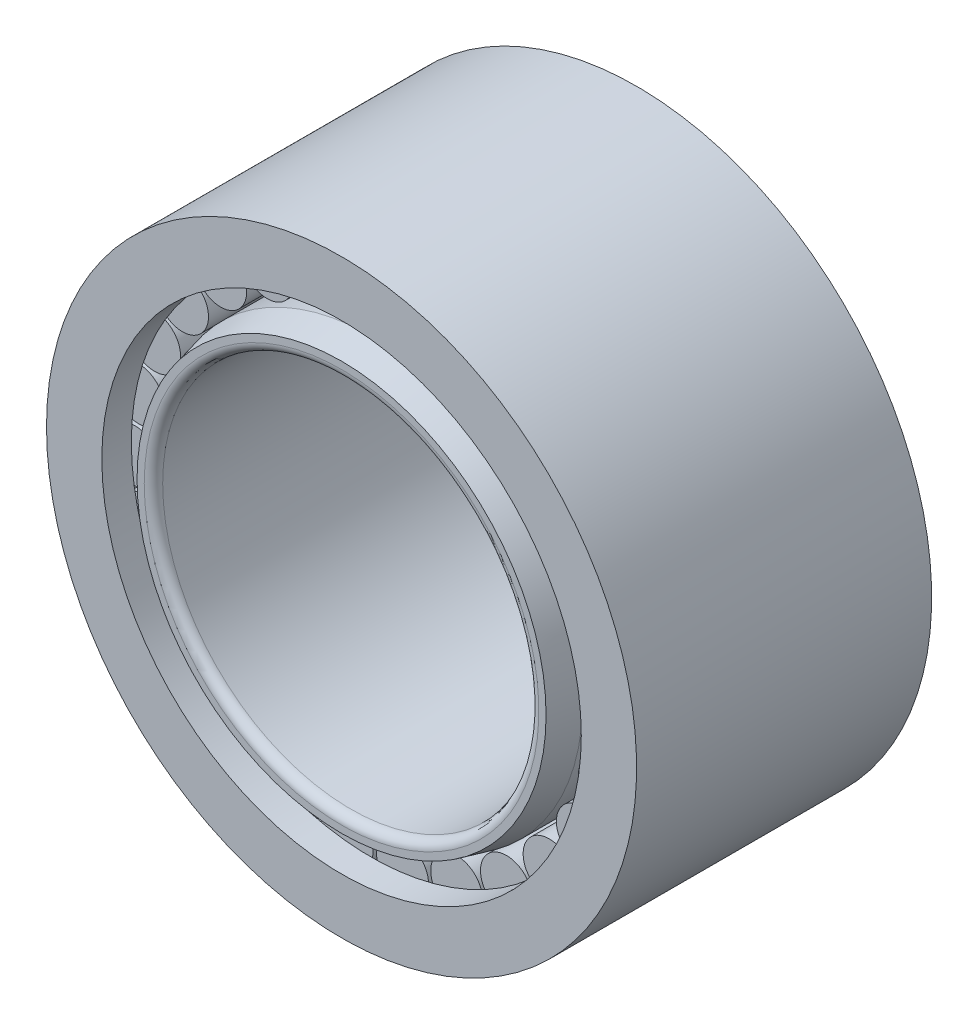
SolidWorks part; units mm, degrees
ref_plane "Front Plane" through (0, 0, 0) normal (0, 0, 1) x (1, 0, 0)
ref_plane "Top Plane" through (0, 0, 0) normal (0, 1, 0) x (1, 0, 0)
ref_plane "Right Plane" through (0, 0, 0) normal (1, 0, 0) x (0, 0, -1)
sketch "Sketch1" plane through (0, 0, 0) normal (1, 0, 0) x (0, 0, -1)
  line L0 (-8, 13) -> (-8, 16)
  line L1 (-8, 16) -> (8, 16)
  line L2 (8, 16) -> (8, 13)
  line L3 (8, 13) -> (6.4, 13)
  line L4 (6.4, 13) -> (6.4, 14.53)
  line L5 (6.4, 14.53) -> (-6.4, 14.53)
  line L6 (-6.4, 14.53) -> (-6.4, 13)
  line L7 (-6.4, 13) -> (-8, 13)
  point P7 (0, 14.53)
  dimension "D1" = 16
  dimension "D2" = 14.53
  dimension "D3" = 13
  dimension "D4" = 1.6
  dimension "D5" = 16
ref_axis "Axis1" through (0, 0, -22) along (0, 0, 1)
revolve "Revolve1" add sketch "Sketch1" angle 360 about axis through (0, 0, -22) along (0, 0, 1)
sketch "Sketch2" plane through (0, 0, 0) normal (1, 0, 0) x (0, 0, -1)
  line L0 (7.5, 10.2) -> (-7.5, 10.2)
  line L1 (-8, 11.09) -> (-6.4, 11.47)
  line L2 (-6.4, 11.47) -> (6.4, 11.47)
  line L3 (6.4, 11.47) -> (8, 11.09)
  line L4 (8, 11.09) -> (8, 10.7)
  line L5 (-8, 11.09) -> (-8, 10.7)
  line L6 (22, 0) -> (-22, 0) construction
  arc A0 (7.5, 10.2) -> (8, 10.7) centre (7.5, 10.7) ccw
  arc A1 (-7.5, 10.2) -> (-8, 10.7) centre (-7.5, 10.7) cw
  point P5 (-8.9478, 11.2)
  point P8 (-8.9515, 11.09)
  point P9 (0, 0)
  point P13 (0, 10.2)
  point P15 (0, 11.47)
  dimension "D1" = 0.5
  dimension "D4" = 10.2
  dimension "D2" = 16
  dimension "D3" = 11.47
  dimension "D5" = 12.8
  dimension "D6" = 11.09
revolve "Revolve2" add sketch "Sketch2" angle 360 about axis through (0, 0, -22) along (0, 0, 1) region at (0, 10.8221, 0)
sketch "Sketch3" plane through (0, 0, 0) normal (1, 0, 0) x (0, 0, -1)
  line L0 (-6.2, 13) -> (-6.2, 14.41)
  line L1 (-6.2, 14.41) -> (6.2, 14.41)
  line L2 (6.2, 14.41) -> (6.2, 13)
  line L3 (6.2, 13) -> (-6.2, 13)
  line L4 (22, 0) -> (-22, 0) construction
  point P4 (0, 13)
  dimension "D1" = 12.4
  dimension "D2" = 1.41
  dimension "D3" = 13
revolve "Revolve3" add sketch "Sketch3" angle 360 about L3
pattern_circular "CirPattern1" count 27 over 360 about axis through (0, 0, -22) along (0, 0, -1) of bodies 103
